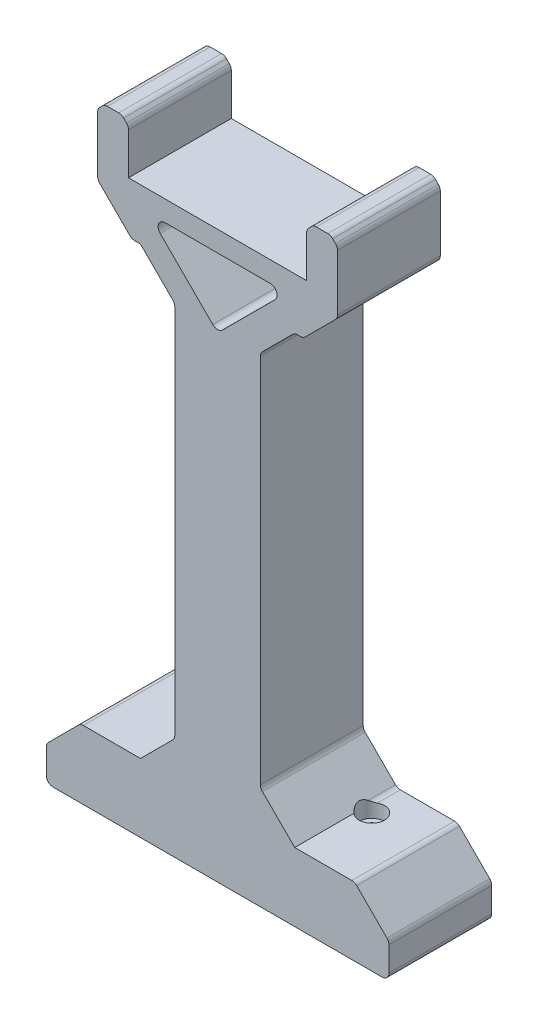
SolidWorks part; units mm, degrees
ref_plane "前视基准面" through (0, 0, 0) normal (0, 0, 1) x (1, 0, 0)
ref_plane "上视基准面" through (0, 0, 0) normal (0, 1, 0) x (1, 0, 0)
ref_plane "右视基准面" through (0, 0, 0) normal (1, 0, 0) x (0, 0, -1)
other "Configuration Table"
sketch "草图2" plane through (0, 0, 0) normal (0, 0, 1) x (1, 0, 0)
  line L0 (0, 0) -> (0, 163.5389) construction
  line L5 (0, 0) -> (117.8973, 0) construction
  line L6 (-35, 180) -> (35, 180)
  line L7 (-35, 180) -> (-35, 150)
  line L8 (-35, 150) -> (-12.5, 150)
  line L9 (-12.5, 150) -> (-12.5, 20)
  line L10 (-12.5, 20) -> (-50, 20)
  line L11 (-50, 20) -> (-50, 0)
  line L12 (-50, 0) -> (50, 0)
  line L13 (50, 20) -> (50, 0)
  line L14 (12.5, 20) -> (50, 20)
  line L15 (12.5, 150) -> (12.5, 20)
  line L16 (35, 150) -> (12.5, 150)
  line L17 (35, 180) -> (35, 150)
  point P18 (0, 180)
  dimension "D1" = 70
  dimension "D2" = 25
  dimension "D3" = 30
  dimension "D4" = 20
  dimension "D5" = 100
  dimension "D6" = 150
extrude "凸台-拉伸1" add sketch "草图2" along normal blind 30
sketch "草图3" plane through (0, 0, 30) normal (0, 0, -1) x (-1, 0, 0)
  line L0 (-35, 180) -> (35, 180) construction
  line L1 (-26, 195) -> (26, 195)
  line L2 (-26, 195) -> (-26, 165)
  line L3 (-26, 165) -> (26, 165)
  line L4 (26, 195) -> (26, 165)
  line L5 (-26, 195) -> (26, 165) construction
  line L6 (-26, 165) -> (26, 195) construction
  point P0 (0, 180)
  dimension "D1" = 52
  dimension "D2" = 30
extrude "切除-拉伸1" cut sketch "草图3" along normal through all
sketch "草图4" plane through (0, 0, 0) normal (0, 0, -1) x (-1, 0, 0)
  line L1 (-40, 10) -> (40, 10)
  line L2 (-40, 10) -> (-40, -10)
  line L3 (-40, -10) -> (40, -10)
  line L4 (40, 10) -> (40, -10)
  line L5 (-40, 10) -> (40, -10) construction
  line L6 (-40, -10) -> (40, 10) construction
  point P0 (0, 0)
  dimension "D1" = 20
  dimension "D2" = 80
extrude "切除-拉伸2" cut sketch "草图4" against normal blind 25
sketch "草图5" plane through (0, 20, 0) normal (0, 1, 0) x (1, 0, 0)
  circle A0 centre (-25, -10) radius 2.15
  circle A1 centre (25, -10) radius 2.15
  dimension "D1" = 4.3
extrude "切除-拉伸3" cut sketch "草图5" against normal through all
sketch "草图6" plane through (0, 20, 0) normal (0, 1, 0) x (1, 0, 0)
  circle A0 centre (25, -10) radius 3.7
  circle A1 centre (-25, -10) radius 3.7
  dimension "D1" = 7.4
extrude "切除-拉伸4" cut sketch "草图6" against normal blind 4
chamfer "倒角1" distance 10 angle 45 8 edges at (-50, 20, 15) (50, 20, 15) (-12.5, 20, 15) (12.5, 20, 15) (-12.5, 150, 15) (12.5, 150, 15) (35, 150, 15) (-35, 150, 15)
chamfer "倒角2" distance 2 angle 45 4 edges at (-35, 180, 15) (-26, 180, 15) (26, 180, 15) (35, 180, 15)
fillet "圆角1" radius 2 30 edges at (-35, 160, 15) (-25, 150, 15) (-22.5, 150, 15) (-12.5, 140, 15) (-12.5, 30, 15) (-22.5, 20, 3.6362) (-40, 20, 15) (-50, 10, 15) (-50, 0, 15) (-40, 0, 12.5) (-40, 10, 12.5) (40, 10, 12.5) (40, 0, 12.5) (50, 0, 15) (50, 10, 15) (40, 20, 15) (22.5, 20, 3.6362) (12.5, 30, 15) (22.5, 150, 15) (25, 150, 15) (35, 160, 15) (35, 178, 15) (33, 180, 15) (28, 180, 15) (26, 178, 15) (-26, 178, 15) (-28, 180, 15) (-33, 180, 15) (-35, 178, 15) (12.5, 140, 15)
sketch "草图7" plane through (0, 0, 0) normal (0, 0, -1) x (-1, 0, 0)
  line L0 (-20.1863, 159) -> (0, 138.8137)
  line L1 (0, 138.8137) -> (20.1863, 159)
  line L2 (20.1863, 159) -> (-20.1863, 159)
  line L3 (0, 138.8137) -> (0, 159) construction
  line L4 (-26, 165) -> (26, 165) construction
  line L5 (13.0858, 140.5858) -> (21.9142, 149.4142) construction
  dimension "D1" = 6
  dimension "D2" = 8
extrude "切除-拉伸5" cut sketch "草图7" against normal through all
fillet "圆角2" radius 2 3 edges at (20.1863, 159, 15) (0, 138.8137, 15) (-20.1863, 159, 15)
